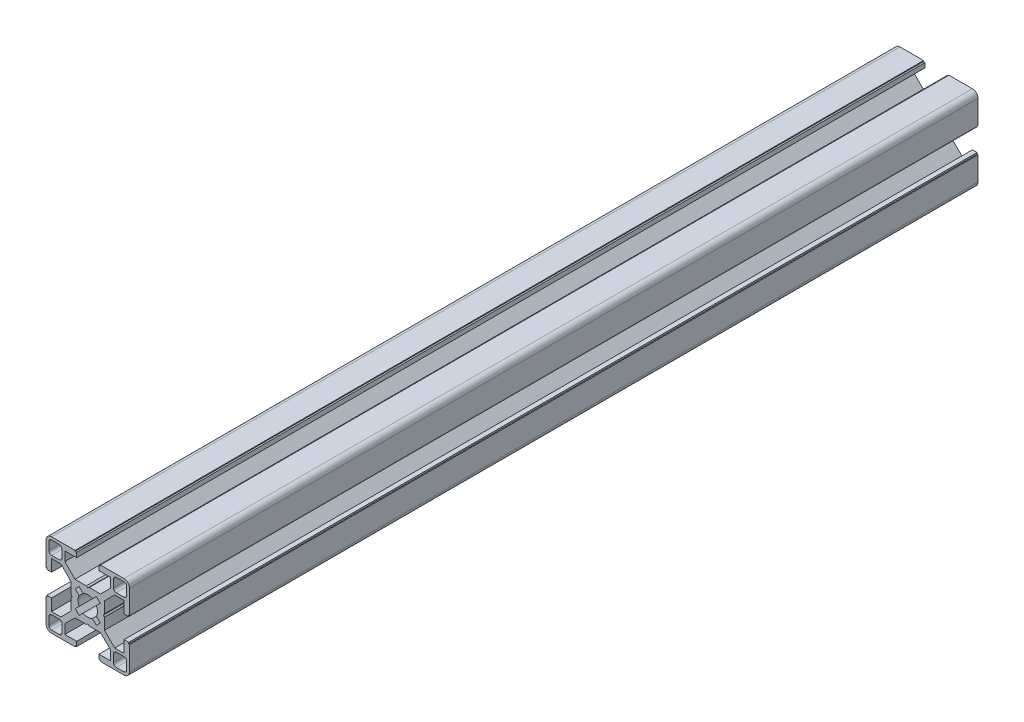
SolidWorks part; units mm, degrees
ref_plane "Front Plane" through (0, 0, 0) normal (0, 0, 1) x (1, 0, 0)
ref_plane "Top Plane" through (0, 0, 0) normal (0, 1, 0) x (1, 0, 0)
ref_plane "Right Plane" through (0, 0, 0) normal (1, 0, 0) x (0, 0, -1)
sketch "Sketch1" plane through (0, 0, 0) normal (0, 0, 1) x (1, 0, 0)
  line L0 (0, 15) -> (0, -15) construction
  line L1 (15, 0) -> (-15, 0) construction
  line L2 (-4.55, 15) -> (4.55, 15) construction
  line L3 (-4, 13) -> (4, 13) construction
  line L4 (-8.25, 8.25) -> (8.25, 8.25) construction
  line L5 (0, 0) -> (-8.25, 8.25) construction
  circle A0 centre (0, 0) radius 3.5 construction
  point P4 (0, 0)
  point P8 (0, 0)
  point P10 (0, 6)
  point P14 (0, 15)
  point P17 (0, 13)
  point P19 (0, 8.25)
sketch "Sketch2" plane through (0, 0, 0) normal (1, 0, 0) x (0, 0, -1)
  line L0 (152.4, 0) -> (-152.4, 0) construction
  point P4 (0, 0)
  dimension "D1" = 304.8
sketch "Sketch3" plane through (0, 0, 0) normal (0, 0, 1) x (1, 0, 0)
  line L9 (-4.55, 15) -> (-4.55, 14.6667)
  line L10 (-4.55, 14.6667) -> (-4, 14.6667)
  line L79 (-4, 14.6667) -> (-4, 13)
  line L80 (-4, 13) -> (-8.25, 13)
  line L81 (0, 0) -> (-8.25, 8.25) construction
  line L108 (4.5858, 6) -> (-4.5858, 6)
  line L113 (-8.25, 13) -> (-8.25, 9.6642)
  line L120 (-8.25, 9.6642) -> (-4.5858, 6)
  line L136 (0, 0) -> (-8.25, 8.25) construction
  line L137 (0, 0) -> (0, 15) construction
  line L138 (8.25, 9.6642) -> (4.5858, 6)
  line L139 (8.25, 13) -> (8.25, 9.6642)
  line L140 (4, 13) -> (8.25, 13)
  line L141 (4, 14.6667) -> (4, 13)
  line L142 (4.55, 14.6667) -> (4, 14.6667)
  line L143 (4.55, 15) -> (4.55, 14.6667)
  line L144 (15, 4.55) -> (14.6667, 4.55)
  line L145 (14.6667, 4.55) -> (14.6667, 4)
  line L146 (14.6667, 4) -> (13, 4)
  line L147 (13, 4) -> (13, 8.25)
  line L148 (6, -4.5858) -> (6, 4.5858)
  line L149 (13, 8.25) -> (9.6642, 8.25)
  line L150 (9.6642, 8.25) -> (6, 4.5858)
  line L151 (9.6642, -8.25) -> (6, -4.5858)
  line L152 (13, -8.25) -> (9.6642, -8.25)
  line L153 (13, -4) -> (13, -8.25)
  line L154 (14.6667, -4) -> (13, -4)
  line L155 (14.6667, -4.55) -> (14.6667, -4)
  line L156 (15, -4.55) -> (14.6667, -4.55)
  line L157 (0, 0) -> (15, 0) construction
  line L158 (4.55, -15) -> (4.55, -14.6667)
  line L159 (4.55, -14.6667) -> (4, -14.6667)
  line L160 (4, -14.6667) -> (4, -13)
  line L179 (4, -13) -> (8.25, -13)
  line L180 (-4.5858, -6) -> (4.5858, -6)
  line L181 (8.25, -13) -> (8.25, -9.6642)
  line L182 (8.25, -9.6642) -> (4.5858, -6)
  line L183 (-8.25, -9.6642) -> (-4.5858, -6)
  line L184 (-8.25, -13) -> (-8.25, -9.6642)
  line L185 (-4, -13) -> (-8.25, -13)
  line L186 (-4, -14.6667) -> (-4, -13)
  line L187 (-4.55, -14.6667) -> (-4, -14.6667)
  line L188 (-4.55, -15) -> (-4.55, -14.6667)
  line L189 (0, 0) -> (0, -15) construction
  line L190 (-15, -4.55) -> (-14.6667, -4.55)
  line L191 (-14.6667, -4.55) -> (-14.6667, -4)
  line L192 (-14.6667, -4) -> (-13, -4)
  line L193 (-13, -4) -> (-13, -8.25)
  line L194 (-6, 4.5858) -> (-6, -4.5858)
  line L195 (-13, -8.25) -> (-9.6642, -8.25)
  line L196 (-9.6642, -8.25) -> (-6, -4.5858)
  line L197 (-9.6642, 8.25) -> (-6, 4.5858)
  line L198 (-13, 8.25) -> (-9.6642, 8.25)
  line L199 (-13, 4) -> (-13, 8.25)
  line L200 (-14.6667, 4) -> (-13, 4)
  line L201 (-14.6667, 4.55) -> (-14.6667, 4)
  line L202 (-15, 4.55) -> (-14.6667, 4.55)
  line L203 (0, 0) -> (-15, 0) construction
  line L204 (0, 0) -> (0, 6) construction
  line L205 (0, 0) -> (6, 0) construction
  line L206 (4.55, 15) -> (13, 15)
  line L207 (15, 13) -> (15, 4.55)
  line L208 (15, -4.55) -> (15, -13)
  line L209 (13, -15) -> (4.55, -15)
  line L210 (-4.55, -15) -> (-13, -15)
  line L211 (-15, -13) -> (-15, -4.55)
  line L212 (-15, 4.55) -> (-15, 13)
  line L213 (-13, 15) -> (-4.55, 15)
  line L214 (-13, 9.25) -> (-10.25, 9.25)
  line L215 (-14, 10.25) -> (-14, 13)
  line L216 (-13, 14) -> (-10.25, 14)
  line L217 (-9.25, 13) -> (-9.25, 10.25)
  line L218 (9.25, 13) -> (9.25, 10.25)
  line L219 (13, 9.25) -> (10.25, 9.25)
  line L220 (10.25, 14) -> (13, 14)
  line L221 (14, 13) -> (14, 10.25)
  line L222 (13, -9.25) -> (10.25, -9.25)
  line L223 (9.25, -13) -> (9.25, -10.25)
  line L224 (14, -10.25) -> (14, -13)
  line L225 (13, -14) -> (10.25, -14)
  line L226 (-9.25, -13) -> (-9.25, -10.25)
  line L227 (-13, -9.25) -> (-10.25, -9.25)
  line L228 (-10.25, -14) -> (-13, -14)
  line L229 (-14, -13) -> (-14, -10.25)
  line L230 (0, 0) -> (-9.25, 10.25) construction
  line L231 (0, 0) -> (10.25, 9.25) construction
  arc A88 (-13, -15) -> (-15, -13) centre (-13, -13) cw
  circle A90 centre (0, 0) radius 3.5 construction
  circle A92 centre (0, 0) radius 3.5
  circle A101 centre (0, 0) radius 3.5
  circle A102 centre (0, 0) radius 3.5
  circle A103 centre (0, 0) radius 3.5
  arc A104 (15, -13) -> (13, -15) centre (13, -13) cw
  arc A105 (13, 15) -> (15, 13) centre (13, 13) cw
  arc A106 (-15, 13) -> (-13, 15) centre (-13, 13) cw
  arc A107 (-9.25, 13) -> (-10.25, 14) centre (-10.25, 13) ccw
  arc A108 (-10.25, 9.25) -> (-9.25, 10.25) centre (-10.25, 10.25) ccw
  arc A109 (-13, 9.25) -> (-14, 10.25) centre (-13, 10.25) cw
  arc A110 (-14, 13) -> (-13, 14) centre (-13, 13) cw
  arc A111 (9.25, 10.25) -> (10.25, 9.25) centre (10.25, 10.25) ccw
  arc A112 (9.25, 13) -> (10.25, 14) centre (10.25, 13) cw
  arc A113 (13, 14) -> (14, 13) centre (13, 13) cw
  arc A114 (13, 9.25) -> (14, 10.25) centre (13, 10.25) ccw
  circle A115 centre (0, 0) radius 3.5
  arc A116 (10.25, -9.25) -> (9.25, -10.25) centre (10.25, -10.25) ccw
  arc A117 (13, -9.25) -> (14, -10.25) centre (13, -10.25) cw
  arc A118 (14, -13) -> (13, -14) centre (13, -13) cw
  arc A119 (9.25, -13) -> (10.25, -14) centre (10.25, -13) ccw
  circle A120 centre (0, 0) radius 3.5
  arc A121 (-9.25, -10.25) -> (-10.25, -9.25) centre (-10.25, -10.25) ccw
  arc A122 (-9.25, -13) -> (-10.25, -14) centre (-10.25, -13) cw
  arc A123 (-13, -14) -> (-14, -13) centre (-13, -13) cw
  arc A124 (-13, -9.25) -> (-14, -10.25) centre (-13, -10.25) ccw
  circle A125 centre (0, 0) radius 3.5
  point P17 (0, 6)
  point P36 (6, 0)
  point P53 (0, -6)
  point P70 (-6, 0)
  point P93 (-11.3321, 8.25)
  point P99 (-9.25, 9.25)
  point P102 (-14, 9.25)
  point P105 (-14, 14)
  dimension "D5" = 2
  dimension "D8" = 1
  dimension "D1" = 0.3333
  dimension "D3" = 90
  dimension "D4" = 2
  dimension "D6" = 1
  dimension "D7" = 1
  dimension "D10" = 90
  dimension "D2" = 4
  dimension "D9" = 4
extrude "Boss-Extrude1" add sketch "Sketch3" along normal up to vertex (152.4 mm away) and the other way up to vertex (152.4 mm away) contours L213 L212 L202 L201 L200 L199 L198 L197 L194 L196 L195 L193 L192 L191 L190 L211 L210 L188 L187 L186 L185 L184 L183 L180 L182 L181 L179 L160 L159 L158 L209 L208 L156 L155 L154 L153 L152 L151 L148 L150 L149 L147 L146 L145 L144 L207 L206 L143 L142 L141 L140 region at (-4.9743, 14.8333, 0) up to point (0, 0, 152.4) other way up to point (0, 0, -152.4)
sketch "Sketch4" plane through (0, 0, 152.4) normal (0, 0, 1) x (1, 0, 0)
  line L0 (0, 0) -> (0, 6) construction
  line L1 (4.5858, 6) -> (-4.5858, 6) construction
  line L2 (-0.5356, 6) -> (0, 5.625)
  line L3 (0.5356, 6) -> (0, 5.625)
  line L4 (-0.5356, 6) -> (0.5356, 6)
  line L5 (6, 0.5356) -> (5.625, 0)
  line L6 (6, -0.5356) -> (5.625, 0)
  line L7 (6, 0.5356) -> (6, -0.5356)
  line L8 (0, 0) -> (6, 0) construction
  line L9 (0.5356, -6) -> (0, -5.625)
  line L10 (-0.5356, -6) -> (0, -5.625)
  line L11 (0.5356, -6) -> (-0.5356, -6)
  line L12 (0, 0) -> (0, -6) construction
  line L13 (-6, -0.5356) -> (-5.625, 0)
  line L14 (-6, 0.5356) -> (-5.625, 0)
  line L15 (-6, -0.5356) -> (-6, 0.5356)
  line L16 (0, 0) -> (-6, 0) construction
  line L17 (0, 0) -> (0, 5.625) construction
  line L18 (0, 0) -> (5.625, 0) construction
  line L19 (-4.493, 3.0788) -> (-3.0788, 1.6646)
  line L20 (-3.0788, 4.493) -> (-1.6646, 3.0788)
  line L21 (-8.25, 9.6642) -> (-4.5858, 6) construction
  line L22 (-9.6642, 8.25) -> (-6, 4.5858) construction
  line L23 (-4.493, 3.0788) -> (-3.0788, 4.493)
  line L24 (3.0788, 4.493) -> (1.6646, 3.0788)
  line L25 (3.0788, 4.493) -> (4.493, 3.0788)
  line L26 (4.493, 3.0788) -> (3.0788, 1.6646)
  line L27 (0, 0) -> (6, 0) construction
  line L28 (4.493, -3.0788) -> (3.0788, -1.6646)
  line L29 (4.493, -3.0788) -> (3.0788, -4.493)
  line L30 (3.0788, -4.493) -> (1.6646, -3.0788)
  line L31 (0, 0) -> (0, -6) construction
  line L32 (-3.0788, -4.493) -> (-1.6646, -3.0788)
  line L33 (-3.0788, -4.493) -> (-4.493, -3.0788)
  line L34 (-4.493, -3.0788) -> (-3.0788, -1.6646)
  line L35 (0, 0) -> (-6, 0) construction
  line L36 (0, 0) -> (-1.6646, 3.0788) construction
  line L37 (0, 0) -> (3.0788, 1.6646) construction
  circle A0 centre (0, 0) radius 3.5 construction
  arc A1 (-1.6646, 3.0788) -> (-3.0788, 1.6646) centre (0, 0) ccw
  arc A2 (-3.0788, -1.6646) -> (-1.6646, -3.0788) centre (0, 0) ccw
  arc A3 (1.6646, -3.0788) -> (3.0788, -1.6646) centre (0, 0) ccw
  arc A4 (3.0788, 1.6646) -> (1.6646, 3.0788) centre (0, 0) ccw
  dimension "D1" = 0.375
  dimension "D2" = 110
  dimension "D4" = 90
  dimension "D5" = 2
  dimension "D7" = 90
  dimension "D3" = 4
  dimension "D6" = 4
extrude "Cut-Extrude1" cut sketch "Sketch4" against normal through all
equation "\"D1@Sketch3\"=\"Wall@Sketch1\"/6"
equation "\"D4@Sketch3\"=\"Wall@Sketch1\""
equation "\"D6@Sketch3\"=\"Wall@Sketch1\"/2"
equation "\"D7@Sketch3\"=\"Wall@Sketch1\"/2"
